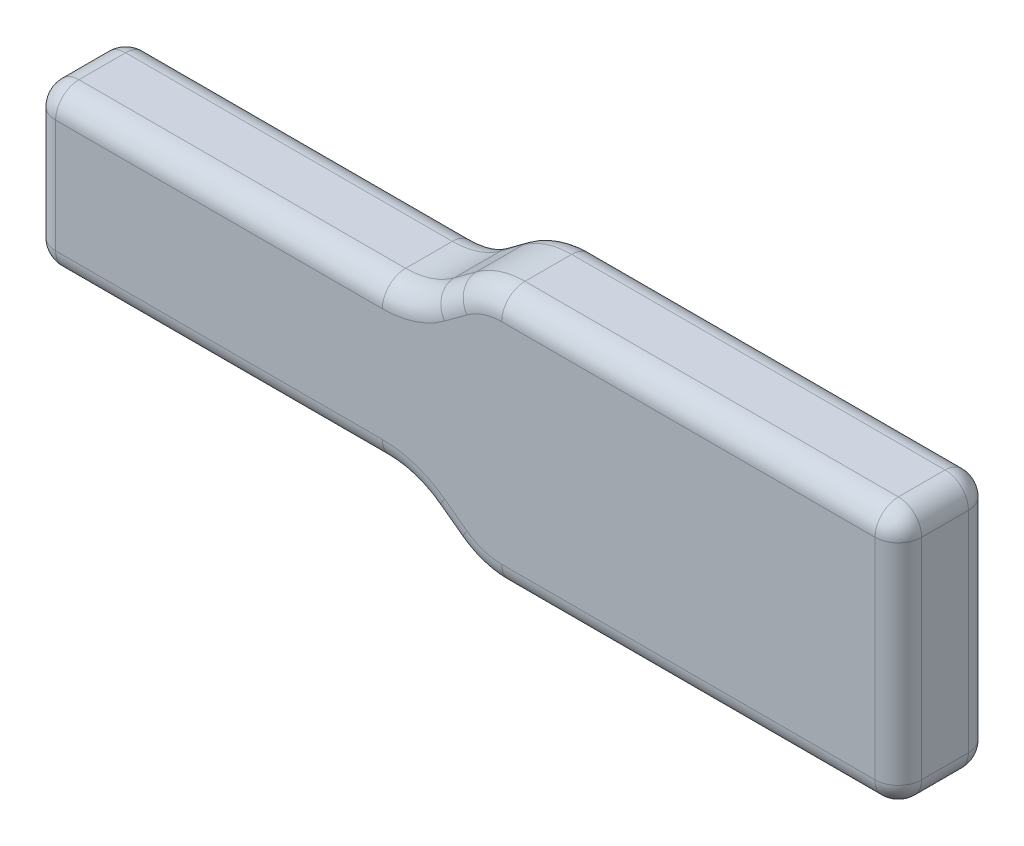
SolidWorks part; units mm, degrees
ref_plane "Front Plane" through (0, 0, 0) normal (0, 0, 1) x (1, 0, 0)
ref_plane "Top Plane" through (0, 0, 0) normal (0, 1, 0) x (1, 0, 0)
ref_plane "Right Plane" through (0, 0, 0) normal (1, 0, 0) x (0, 0, -1)
sketch "Sketch2" plane through (0, 0, 0) normal (0, 0, 1) x (1, 0, 0)
  line L0 (0, 20) -> (-32, 20)
  line L1 (-36.1576, 18.6316) -> (-38.0717, 17.2184)
  line L2 (-42.2293, 15.85) -> (-70.2293, 15.85)
  line L3 (-72.2293, 13.85) -> (-72.2293, 4.15)
  line L4 (-70.2293, 2.15) -> (-42.2293, 2.15)
  line L5 (-38.0717, 0.7816) -> (-36.1576, -0.6316)
  line L6 (-32, -2) -> (0, -2)
  line L7 (2, 0) -> (2, 18)
  arc A0 (-36.1576, -0.6316) -> (-32, -2) centre (-32, 5) ccw
  arc A1 (-42.2293, 2.15) -> (-38.0717, 0.7816) centre (-42.2293, -4.85) cw
  arc A2 (-38.0717, 17.2184) -> (-42.2293, 15.85) centre (-42.2293, 22.85) cw
  arc A3 (-32, 20) -> (-36.1576, 18.6316) centre (-32, 13) ccw
  arc A4 (0, -2) -> (2, 0) centre (0, 0) ccw
  arc A5 (0, 20) -> (2, 18) centre (0, 18) cw
  arc A6 (-72.2293, 4.15) -> (-70.2293, 2.15) centre (-70.2293, 4.15) ccw
  arc A7 (-70.2293, 15.85) -> (-72.2293, 13.85) centre (-70.2293, 13.85) ccw
  dimension "D1" = 7
  dimension "D2" = 2
  dimension "D3" = 2
  dimension "D4" = 28
  dimension "D5" = 32
  dimension "D7" = 9.7
  dimension "D9" = 0
  dimension "longer_base" = 18
extrude "Boss-Extrude2" add sketch "Sketch2" along normal blind 8
shell "Shell1" thickness 1 removed face at (-72.2293, 9, 4)
sketch "Sketch5" plane through (-72.2293, 0, 0) normal (-1, 0, 0) x (0, 0, 1)
  line L0 (7, 13.85) -> (1, 13.85) construction
  line L1 (1, 13.85) -> (1, 4.15) construction
  line L2 (7, 13.85) -> (7, 4.15) construction
  line L3 (7, 4.15) -> (1, 4.15) construction
  line L4 (7, 13.85) -> (1, 13.85)
  line L5 (1, 13.85) -> (1, 4.15)
  line L6 (7, 13.85) -> (7, 4.15)
  line L7 (7, 4.15) -> (1, 4.15)
extrude "Boss-Extrude4" add sketch "Sketch5" against normal blind 1
fillet "Fillet1" radius 2 32 edges at (-40.0408, 16.2009, 0) (-37.1146, 17.925, 0) (-34.1885, 19.6491, 0) (-16, 20, 0) (1.4142, 19.4142, 0) (2, 9, 0) (1.4142, -1.4142, 0) (-16, -2, 0) (-34.1885, -1.6491, 0) (-37.1146, 0.075, 0) (-40.0408, 1.7991, 0) (-56.2293, 2.15, 0) (-71.6435, 2.7358, 0) (-72.2293, 9, 0) (-71.6435, 15.2642, 0) (-56.2293, 15.85, 8) (-40.0408, 16.2009, 8) (-37.1146, 17.925, 8) (-34.1885, 19.6491, 8) (-16, 20, 8) (1.4142, 19.4142, 8) (2, 9, 8) (1.4142, -1.4142, 8) (-16, -2, 8) (-34.1885, -1.6491, 8) (-37.1146, 0.075, 8) (-40.0408, 1.7991, 8) (-56.2293, 2.15, 8) (-71.6435, 2.7358, 8) (-72.2293, 9, 8) (-56.2293, 15.85, 0) (-71.6435, 15.2642, 8)
sketch "Sketch7" plane through (0, 0, 8) normal (0, 0, 1) x (1, 0, 0)
  line L0 (0, 18) -> (-32, 18) construction
  line L1 (0, 0) -> (0, 18) construction
  circle A0 centre (-5, 9) radius 2.4323
  point P4 (0, 9)
  dimension "D1" = 9
  dimension "D2" = 5
